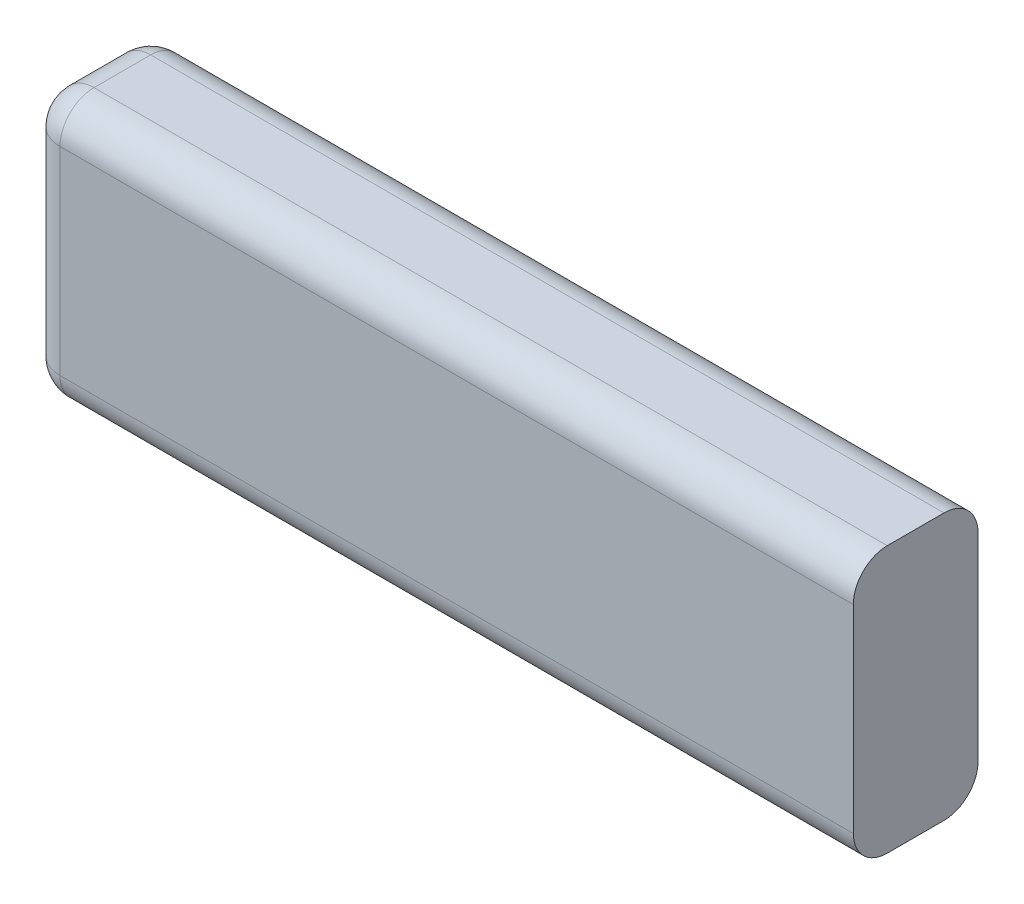
SolidWorks part; units mm, degrees
ref_plane "Front" through (0, 0, 0) normal (0, 0, 1) x (1, 0, 0)
ref_plane "Top" through (0, 0, 0) normal (0, 1, 0) x (1, 0, 0)
ref_plane "Right" through (0, 0, 0) normal (1, 0, 0) x (0, 0, -1)
sketch "Sketch1" plane through (0, 0, 0) normal (0, 0, 1) x (1, 0, 0)
  line L1 (0, 0) -> (36.5, 0)
  line L2 (0, 0) -> (0, 11.75)
  line L3 (0, 11.75) -> (36.5, 11.75)
  line L4 (36.5, 0) -> (36.5, 11.75)
  dimension "D1" = 11.75
  dimension "D2" = 36.5
extrude "Boss-Extrude1" add sketch "Sketch1" along normal blind 5.5
fillet "Fillet1" radius 1.5 8 edges at (18.25, 0, 0) (18.25, 0, 5.5) (0, 0, 2.75) (0, 5.875, 0) (0, 5.875, 5.5) (18.25, 11.75, 0) (18.25, 11.75, 5.5) (0, 11.75, 2.75)
